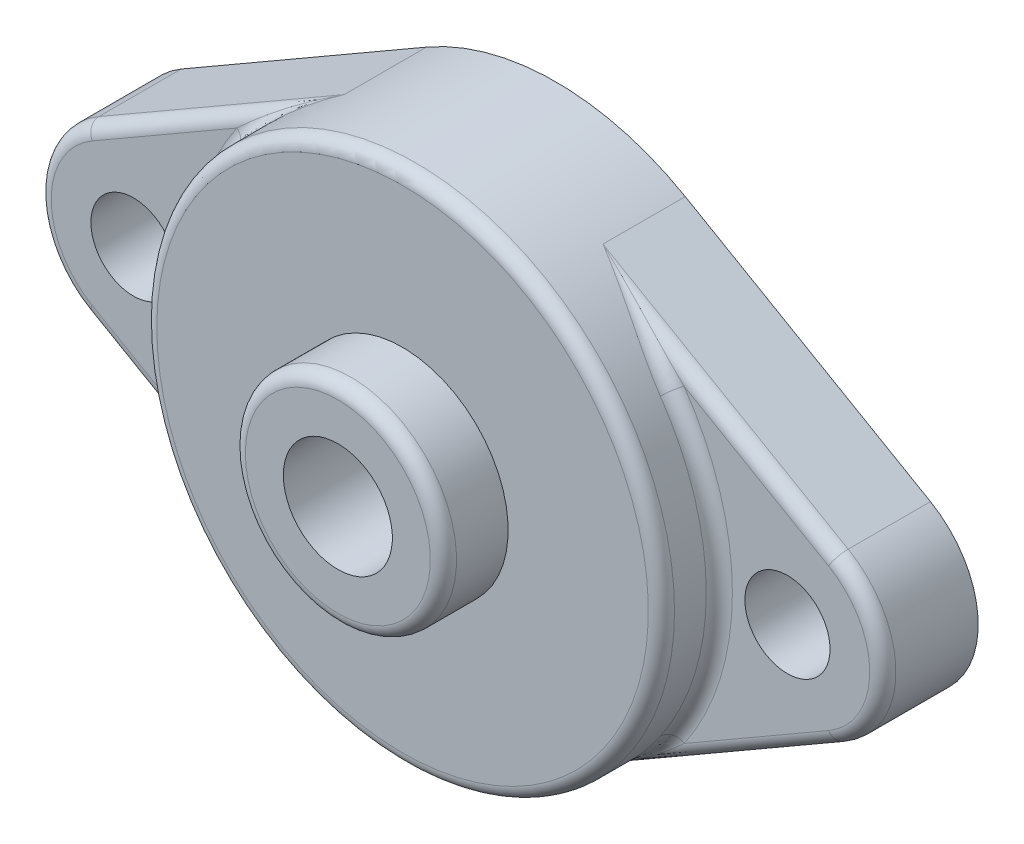
SolidWorks part; units mm, degrees
ref_plane "Front" through (0, 0, 0) normal (0, 0, 1) x (1, 0, 0)
ref_plane "Top" through (0, 0, 0) normal (0, 1, 0) x (1, 0, 0)
ref_plane "Right" through (0, 0, 0) normal (1, 0, 0) x (0, 0, -1)
sketch "Sketch1" plane through (0, 0, 0) normal (0, 0, 1) x (1, 0, 0)
  line L0 (0, 0) -> (0, 47.9638) construction
  line L1 (-38.1, 0) -> (38.1, 0) construction
  line L2 (15.0812, 26.1215) -> (43.6562, 9.6237)
  line L3 (15.0812, -26.1215) -> (43.6562, -9.6237)
  line L4 (-15.0812, 26.1215) -> (-43.6562, 9.6237)
  line L5 (-15.0812, -26.1215) -> (-43.6562, -9.6237)
  arc A0 (15.0812, 26.1215) -> (-15.0812, 26.1215) centre (0, 0) ccw
  circle A2 centre (38.1, 0) radius 4.9609
  circle A3 centre (-38.1, 0) radius 4.9609
  arc A4 (43.6562, -9.6237) -> (43.6562, 9.6237) centre (38.1, 0) ccw
  arc A5 (-43.6562, -9.6237) -> (-43.6562, 9.6237) centre (-38.1, 0) cw
  arc A6 (-15.0812, -26.1215) -> (15.0812, -26.1215) centre (0, 0) ccw
  dimension "L" = 60.325
  dimension "N" = 9.9219
  dimension "H-J" = 22.225
  dimension "J" = 76.2
extrude "Base-Extrude" add sketch "Sketch1" along normal blind 11.1125
sketch "Sketch2" plane through (0, 0, 0) normal (0, 0, -1) x (-1, 0, 0)
  circle A0 centre (0, 0) radius 30.1625
  arc A1 (15.0812, 26.1215) -> (-15.0812, 26.1215) centre (0, 0) ccw construction
extrude "Boss-Extrude1" add sketch "Sketch2" against normal blind 17.8594
sketch "Sketch3" plane through (0, 0, 0) normal (0, 0, -1) x (-1, 0, 0)
  circle A0 centre (0, 0) radius 12.3031
  dimension "F" = 24.6062
extrude "Boss-Extrude2" add sketch "Sketch3" against normal blind 25.4
sketch "Sketch4" plane through (0, 0, 0) normal (0, 0, -1) x (-1, 0, 0)
  circle A0 centre (0, 0) radius 6.35
  dimension "Bore" = 12.7
extrude "Cut-Extrude1" cut sketch "Sketch4" against normal through all
fillet "Fillet1" radius 1.524 10 edges at (-30.1625, 0, 17.8594) (-29.3688, -17.8726, 11.1125) (29.3687, -17.8726, 11.1125) (-49.2125, 0, 11.1125) (49.2125, 0, 11.1125) (-30.1625, 0, 11.1125) (-29.3687, 17.8726, 11.1125) (30.1625, 0, 11.1125) (29.3687, 17.8726, 11.1125) (-12.3031, 0, 25.4)
